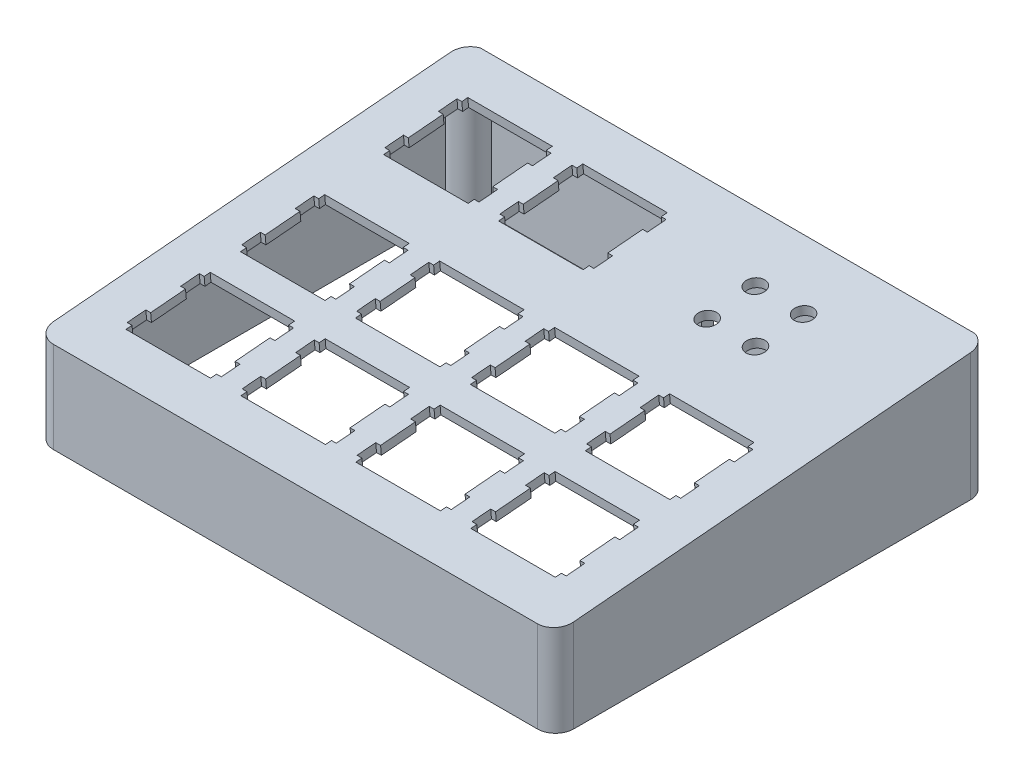
SolidWorks part; units mm, degrees
material "ABS"
ref_plane "Front" through (0, 0, 0) normal (0, 0, 1) x (1, 0, 0)
ref_plane "Top" through (0, 0, 0) normal (0, 1, 0) x (1, 0, 0)
ref_plane "Right" through (0, 0, 0) normal (1, 0, 0) x (0, 0, -1)
ref_axis "Axis1" through (80.9, 0, 0) along (-1, 0, 0)
ref_plane "Plane1" through (0, 0, 0) normal (0, 0.9962, 0.0872) x (1, 0, 0)
sketch "Sketch2" plane through (0, 0, 0) normal (0, 0.9962, 0.0872) x (1, 0, 0)
  line L1 (-43.1005, -35.9565) -> (43.1005, -35.9565)
  line L2 (-43.1005, -35.9565) -> (-43.1005, 35.9565)
  line L3 (-43.1005, 35.9565) -> (43.1005, 35.9565)
  line L4 (43.1005, -35.9565) -> (43.1005, 35.9565)
  line L5 (-43.1005, -35.9565) -> (43.1005, 35.9565) construction
  line L6 (-43.1005, 35.9565) -> (43.1005, -35.9565) construction
  point P0 (0, 0)
  dimension "D1" = 71.913
  dimension "D2" = 86.201
extrude "Boss-Extrude1" add sketch "Sketch2" along normal mid plane 1.5
sketch "Sketch7" plane through (0, 0.7471, 0.0654) normal (0, 0.9962, 0.0872) x (1, 0, 0)
  line L0 (16.5245, -2.3805) -> (21.5745, -2.3805) construction
  line L1 (19.0495, -2.3805) -> (19.0495, 21.432) construction
  line L2 (15.0495, 25.432) -> (23.0495, 25.432) construction
  line L3 (15.0495, 25.432) -> (15.0495, 17.432) construction
  line L4 (15.0495, 17.432) -> (23.0495, 17.432) construction
  line L5 (23.0495, 25.432) -> (23.0495, 17.432) construction
  line L6 (15.0495, 25.432) -> (23.0495, 17.432) construction
  line L7 (15.0495, 17.432) -> (23.0495, 25.432) construction
  line L8 (-43.1005, 35.9565) -> (-43.1005, -35.9565) construction
  line L9 (-43.1005, -35.9565) -> (43.1005, -35.9565) construction
  circle A0 centre (15.0495, 25.432) radius 1.5635
  circle A1 centre (23.0495, 25.432) radius 1.5635
  circle A2 centre (23.0495, 17.432) radius 1.5635
  circle A3 centre (15.0495, 17.432) radius 1.5635
  point P5 (-2.5255, 21.432)
  line B0 (43.1005, -35.9565) -> (-43.1005, -35.9565)
  line B1 (-43.1005, -35.9565) -> (-43.1005, 35.9565)
  line B2 (-43.1005, 35.9565) -> (43.1005, 35.9565)
  line B3 (43.1005, 35.9565) -> (43.1005, -35.9565)
  line B4 (21.5745, -14.4305) -> (21.5745, -15.4305)
  line B5 (21.5745, -15.4305) -> (20.7745, -15.4305)
  line B6 (20.7745, -15.4305) -> (20.7745, -18.5305)
  line B7 (20.7745, -18.5305) -> (21.5745, -18.5305)
  line B8 (21.5745, -18.5305) -> (21.5745, -24.3305)
  line B9 (21.5745, -24.3305) -> (20.7745, -24.3305)
  line B10 (20.7745, -24.3305) -> (20.7745, -27.4305)
  line B11 (20.7745, -27.4305) -> (21.5745, -27.4305)
  line B12 (21.5745, -27.4305) -> (21.5745, -28.4305)
  line B13 (21.5745, -28.4305) -> (35.5745, -28.4305)
  line B14 (35.5745, -28.4305) -> (35.5745, -27.4305)
  line B15 (35.5745, -27.4305) -> (36.3745, -27.4305)
  line B16 (36.3745, -27.4305) -> (36.3745, -24.3305)
  line B17 (36.3745, -24.3305) -> (35.5745, -24.3305)
  line B18 (35.5745, -24.3305) -> (35.5745, -18.5305)
  line B19 (35.5745, -18.5305) -> (36.3745, -18.5305)
  line B20 (36.3745, -18.5305) -> (36.3745, -15.4305)
  line B21 (36.3745, -15.4305) -> (35.5745, -15.4305)
  line B22 (35.5745, -15.4305) -> (35.5745, -14.4305)
  line B23 (35.5745, -14.4305) -> (21.5745, -14.4305)
  line B24 (2.5245, -14.4305) -> (2.5245, -15.4305)
  line B25 (2.5245, -15.4305) -> (1.7245, -15.4305)
  line B26 (1.7245, -15.4305) -> (1.7245, -18.5305)
  line B27 (1.7245, -18.5305) -> (2.5245, -18.5305)
  line B28 (2.5245, -18.5305) -> (2.5245, -24.3305)
  line B29 (2.5245, -24.3305) -> (1.7245, -24.3305)
  line B30 (1.7245, -24.3305) -> (1.7245, -27.4305)
  line B31 (1.7245, -27.4305) -> (2.5245, -27.4305)
  line B32 (2.5245, -27.4305) -> (2.5245, -28.4305)
  line B33 (2.5245, -28.4305) -> (16.5245, -28.4305)
  line B34 (16.5245, -28.4305) -> (16.5245, -27.4305)
  line B35 (16.5245, -27.4305) -> (17.3245, -27.4305)
  line B36 (17.3245, -27.4305) -> (17.3245, -24.3305)
  line B37 (17.3245, -24.3305) -> (16.5245, -24.3305)
  line B38 (16.5245, -24.3305) -> (16.5245, -18.5305)
  line B39 (16.5245, -18.5305) -> (17.3245, -18.5305)
  line B40 (17.3245, -18.5305) -> (17.3245, -15.4305)
  line B41 (17.3245, -15.4305) -> (16.5245, -15.4305)
  line B42 (16.5245, -15.4305) -> (16.5245, -14.4305)
  line B43 (16.5245, -14.4305) -> (2.5245, -14.4305)
  line B44 (-16.5255, -14.4305) -> (-16.5255, -15.4305)
  line B45 (-16.5255, -15.4305) -> (-17.3255, -15.4305)
  line B46 (-17.3255, -15.4305) -> (-17.3255, -18.5305)
  line B47 (-17.3255, -18.5305) -> (-16.5255, -18.5305)
  line B48 (-16.5255, -18.5305) -> (-16.5255, -24.3305)
  line B49 (-16.5255, -24.3305) -> (-17.3255, -24.3305)
  line B50 (-17.3255, -24.3305) -> (-17.3255, -27.4305)
  line B51 (-17.3255, -27.4305) -> (-16.5255, -27.4305)
  line B52 (-16.5255, -27.4305) -> (-16.5255, -28.4305)
  line B53 (-16.5255, -28.4305) -> (-2.5255, -28.4305)
  line B54 (-2.5255, -28.4305) -> (-2.5255, -27.4305)
  line B55 (-2.5255, -27.4305) -> (-1.7255, -27.4305)
  line B56 (-1.7255, -27.4305) -> (-1.7255, -24.3305)
  line B57 (-1.7255, -24.3305) -> (-2.5255, -24.3305)
  line B58 (-2.5255, -24.3305) -> (-2.5255, -18.5305)
  line B59 (-2.5255, -18.5305) -> (-1.7255, -18.5305)
  line B60 (-1.7255, -18.5305) -> (-1.7255, -15.4305)
  line B61 (-1.7255, -15.4305) -> (-2.5255, -15.4305)
  line B62 (-2.5255, -15.4305) -> (-2.5255, -14.4305)
  line B63 (-2.5255, -14.4305) -> (-16.5255, -14.4305)
  line B64 (-35.5765, -14.4305) -> (-35.5765, -15.4305)
  line B65 (-35.5765, -15.4305) -> (-36.3765, -15.4305)
  line B66 (-36.3765, -15.4305) -> (-36.3765, -18.5305)
  line B67 (-36.3765, -18.5305) -> (-35.5765, -18.5305)
  line B68 (-35.5765, -18.5305) -> (-35.5765, -24.3305)
  line B69 (-35.5765, -24.3305) -> (-36.3765, -24.3305)
  line B70 (-36.3765, -24.3305) -> (-36.3765, -27.4305)
  line B71 (-36.3765, -27.4305) -> (-35.5765, -27.4305)
  line B72 (-35.5765, -27.4305) -> (-35.5765, -28.4305)
  line B73 (-35.5765, -28.4305) -> (-21.5755, -28.4305)
  line B74 (-21.5755, -28.4305) -> (-21.5755, -27.4305)
  line B75 (-21.5755, -27.4305) -> (-20.7755, -27.4305)
  line B76 (-20.7755, -27.4305) -> (-20.7755, -24.3305)
  line B77 (-20.7755, -24.3305) -> (-21.5755, -24.3305)
  line B78 (-21.5755, -24.3305) -> (-21.5755, -18.5305)
  line B79 (-21.5755, -18.5305) -> (-20.7755, -18.5305)
  line B80 (-20.7755, -18.5305) -> (-20.7755, -15.4305)
  line B81 (-20.7755, -15.4305) -> (-21.5755, -15.4305)
  line B82 (-21.5755, -15.4305) -> (-21.5755, -14.4305)
  line B83 (-21.5755, -14.4305) -> (-35.5765, -14.4305)
  line B84 (21.5745, 4.6195) -> (21.5745, 3.6195)
  line B85 (21.5745, 3.6195) -> (20.7745, 3.6195)
  line B86 (20.7745, 3.6195) -> (20.7745, 0.5195)
  line B87 (20.7745, 0.5195) -> (21.5745, 0.5195)
  line B88 (21.5745, 0.5195) -> (21.5745, -5.2805)
  line B89 (21.5745, -5.2805) -> (20.7745, -5.2805)
  line B90 (20.7745, -5.2805) -> (20.7745, -8.3805)
  line B91 (20.7745, -8.3805) -> (21.5745, -8.3805)
  line B92 (21.5745, -8.3805) -> (21.5745, -9.3805)
  line B93 (21.5745, -9.3805) -> (35.5745, -9.3805)
  line B94 (35.5745, -9.3805) -> (35.5745, -8.3805)
  line B95 (35.5745, -8.3805) -> (36.3745, -8.3805)
  line B96 (36.3745, -8.3805) -> (36.3745, -5.2805)
  line B97 (36.3745, -5.2805) -> (35.5745, -5.2805)
  line B98 (35.5745, -5.2805) -> (35.5745, 0.5195)
  line B99 (35.5745, 0.5195) -> (36.3745, 0.5195)
  line B100 (36.3745, 0.5195) -> (36.3745, 3.6195)
  line B101 (36.3745, 3.6195) -> (35.5745, 3.6195)
  line B102 (35.5745, 3.6195) -> (35.5745, 4.6195)
  line B103 (35.5745, 4.6195) -> (21.5745, 4.6195)
  line B104 (2.5245, 4.6195) -> (2.5245, 3.6195)
  line B105 (2.5245, 3.6195) -> (1.7245, 3.6195)
  line B106 (1.7245, 3.6195) -> (1.7245, 0.5195)
  line B107 (1.7245, 0.5195) -> (2.5245, 0.5195)
  line B108 (2.5245, 0.5195) -> (2.5245, -5.2805)
  line B109 (2.5245, -5.2805) -> (1.7245, -5.2805)
  line B110 (1.7245, -5.2805) -> (1.7245, -8.3805)
  line B111 (1.7245, -8.3805) -> (2.5245, -8.3805)
  line B112 (2.5245, -8.3805) -> (2.5245, -9.3805)
  line B113 (2.5245, -9.3805) -> (16.5245, -9.3805)
  line B114 (16.5245, -9.3805) -> (16.5245, -8.3805)
  line B115 (16.5245, -8.3805) -> (17.3245, -8.3805)
  line B116 (17.3245, -8.3805) -> (17.3245, -5.2805)
  line B117 (17.3245, -5.2805) -> (16.5245, -5.2805)
  line B118 (16.5245, -5.2805) -> (16.5245, 0.5195)
  line B119 (16.5245, 0.5195) -> (17.3245, 0.5195)
  line B120 (17.3245, 0.5195) -> (17.3245, 3.6195)
  line B121 (17.3245, 3.6195) -> (16.5245, 3.6195)
  line B122 (16.5245, 3.6195) -> (16.5245, 4.6195)
  line B123 (16.5245, 4.6195) -> (2.5245, 4.6195)
  line B124 (-16.5255, 4.6195) -> (-16.5255, 3.6195)
  line B125 (-16.5255, 3.6195) -> (-17.3255, 3.6195)
  line B126 (-17.3255, 3.6195) -> (-17.3255, 0.5195)
  line B127 (-17.3255, 0.5195) -> (-16.5255, 0.5195)
  line B128 (-16.5255, 0.5195) -> (-16.5255, -5.2805)
  line B129 (-16.5255, -5.2805) -> (-17.3255, -5.2805)
  line B130 (-17.3255, -5.2805) -> (-17.3255, -8.3805)
  line B131 (-17.3255, -8.3805) -> (-16.5255, -8.3805)
  line B132 (-16.5255, -8.3805) -> (-16.5255, -9.3805)
  line B133 (-16.5255, -9.3805) -> (-2.5255, -9.3805)
  line B134 (-2.5255, -9.3805) -> (-2.5255, -8.3805)
  line B135 (-2.5255, -8.3805) -> (-1.7255, -8.3805)
  line B136 (-1.7255, -8.3805) -> (-1.7255, -5.2805)
  line B137 (-1.7255, -5.2805) -> (-2.5255, -5.2805)
  line B138 (-2.5255, -5.2805) -> (-2.5255, 0.5195)
  line B139 (-2.5255, 0.5195) -> (-1.7255, 0.5195)
  line B140 (-1.7255, 0.5195) -> (-1.7255, 3.6195)
  line B141 (-1.7255, 3.6195) -> (-2.5255, 3.6195)
  line B142 (-2.5255, 3.6195) -> (-2.5255, 4.6195)
  line B143 (-2.5255, 4.6195) -> (-16.5255, 4.6195)
  line B144 (-35.5765, 4.6195) -> (-35.5765, 3.6195)
  line B145 (-35.5765, 3.6195) -> (-36.3765, 3.6195)
  line B146 (-36.3765, 3.6195) -> (-36.3765, 0.5195)
  line B147 (-36.3765, 0.5195) -> (-35.5765, 0.5195)
  line B148 (-35.5765, 0.5195) -> (-35.5765, -5.2805)
  line B149 (-35.5765, -5.2805) -> (-36.3765, -5.2805)
  line B150 (-36.3765, -5.2805) -> (-36.3765, -8.3805)
  line B151 (-36.3765, -8.3805) -> (-35.5765, -8.3805)
  line B152 (-35.5765, -8.3805) -> (-35.5765, -9.3805)
  line B153 (-35.5765, -9.3805) -> (-21.5755, -9.3805)
  line B154 (-21.5755, -9.3805) -> (-21.5755, -8.3805)
  line B155 (-21.5755, -8.3805) -> (-20.7755, -8.3805)
  line B156 (-20.7755, -8.3805) -> (-20.7755, -5.2805)
  line B157 (-20.7755, -5.2805) -> (-21.5755, -5.2805)
  line B158 (-21.5755, -5.2805) -> (-21.5755, 0.5195)
  line B159 (-21.5755, 0.5195) -> (-20.7755, 0.5195)
  line B160 (-20.7755, 0.5195) -> (-20.7755, 3.6195)
  line B161 (-20.7755, 3.6195) -> (-21.5755, 3.6195)
  line B162 (-21.5755, 3.6195) -> (-21.5755, 4.6195)
  line B163 (-21.5755, 4.6195) -> (-35.5765, 4.6195)
  line B164 (-16.5255, 28.4325) -> (-16.5255, 27.4325)
  line B165 (-16.5255, 27.4325) -> (-17.3255, 27.4325)
  line B166 (-17.3255, 27.4325) -> (-17.3255, 24.3315)
  line B167 (-17.3255, 24.3315) -> (-16.5255, 24.3315)
  line B168 (-16.5255, 24.3315) -> (-16.5255, 18.5325)
  line B169 (-16.5255, 18.5325) -> (-17.3255, 18.5325)
  line B170 (-17.3255, 18.5325) -> (-17.3255, 15.4315)
  line B171 (-17.3255, 15.4315) -> (-16.5255, 15.4315)
  line B172 (-16.5255, 15.4315) -> (-16.5255, 14.4315)
  line B173 (-16.5255, 14.4315) -> (-2.5255, 14.4315)
  line B174 (-2.5255, 14.4315) -> (-2.5255, 15.4315)
  line B175 (-2.5255, 15.4315) -> (-1.7255, 15.4315)
  line B176 (-1.7255, 15.4315) -> (-1.7255, 18.5325)
  line B177 (-1.7255, 18.5325) -> (-2.5255, 18.5325)
  line B178 (-2.5255, 18.5325) -> (-2.5255, 24.3315)
  line B179 (-2.5255, 24.3315) -> (-1.7255, 24.3315)
  line B180 (-1.7255, 24.3315) -> (-1.7255, 27.4325)
  line B181 (-1.7255, 27.4325) -> (-2.5255, 27.4325)
  line B182 (-2.5255, 27.4325) -> (-2.5255, 28.4325)
  line B183 (-2.5255, 28.4325) -> (-16.5255, 28.4325)
  line B184 (-35.5765, 28.4325) -> (-35.5765, 27.4325)
  line B185 (-35.5765, 27.4325) -> (-36.3765, 27.4325)
  line B186 (-36.3765, 27.4325) -> (-36.3765, 24.3315)
  line B187 (-36.3765, 24.3315) -> (-35.5765, 24.3315)
  line B188 (-35.5765, 24.3315) -> (-35.5765, 18.5325)
  line B189 (-35.5765, 18.5325) -> (-36.3765, 18.5325)
  line B190 (-36.3765, 18.5325) -> (-36.3765, 15.4315)
  line B191 (-36.3765, 15.4315) -> (-35.5765, 15.4315)
  line B192 (-35.5765, 15.4315) -> (-35.5765, 14.4315)
  line B193 (-35.5765, 14.4315) -> (-21.5755, 14.4315)
  line B194 (-21.5755, 14.4315) -> (-21.5755, 15.4315)
  line B195 (-21.5755, 15.4315) -> (-20.7755, 15.4315)
  line B196 (-20.7755, 15.4315) -> (-20.7755, 18.5325)
  line B197 (-20.7755, 18.5325) -> (-21.5755, 18.5325)
  line B198 (-21.5755, 18.5325) -> (-21.5755, 24.3315)
  line B199 (-21.5755, 24.3315) -> (-20.7755, 24.3315)
  line B200 (-20.7755, 24.3315) -> (-20.7755, 27.4325)
  line B201 (-20.7755, 27.4325) -> (-21.5755, 27.4325)
  line B202 (-21.5755, 27.4325) -> (-21.5755, 28.4325)
  line B203 (-21.5755, 28.4325) -> (-35.5765, 28.4325)
  dimension "D1" = 3.127
  dimension "D2" = 8
sketch_block_instance "Block1-1"
sketch_block "Block1"
extrude "Cut-Extrude1" cut sketch "Sketch7" against normal up to next contours B42 B43 B24 B25 B26 B27 B28 B29 B30 B31 B32 B33 B34 B35 B36 B37 B38 B39 B40 B41 | B22 B23 B4 B5 B6 B7 B8 B9 B10 B11 B12 B13 B14 B15 B16 B17 B18 B19 B20 B21 | B122 B123 B104 B105 B106 B107 B108 B109 B110 B111 B112 B113 B114 B115 B116 B117 B118 B119 B120 B121 | B62 B63 B44 B45 B46 B47 B48 B49 B50 B51 B52 B53 B54 B55 B56 B57 B58 B59 B60 B61 | B142 B143 B124 B125 B126 B127 B128 B129 B130 B131 B132 B133 B134 B135 B136 B137 B138 B139 B140 B141 | B82 B83 B64 B65 B66 B67 B68 B69 B70 B71 B72 B73 B74 B75 B76 B77 B78 B79 B80 B81 | B162 B163 B144 B145 B146 B147 B148 B149 B150 B151 B152 B153 B154 B155 B156 B157 B158 B159 B160 B161 | B102 B103 B84 B85 B86 B87 B88 B89 B90 B91 B92 B93 B94 B95 B96 B97 B98 B99 B100 B101 | B202 B203 B184 B185 B186 B187 B188 B189 B190 B191 B192 B193 B194 B195 B196 B197 B198 B199 B200 B201 | B182 B183 B164 B165 B166 B167 B168 B169 B170 B171 B172 B173 B174 B175 B176 B177 B178 B179 B180 B181 | A3 | A0 | A1 | A2 region at (15.0495, 2.9637, -25.2699) region at (23.0495, 2.9637, -25.2699) region at (23.0495, 2.2664, -17.3003) region at (15.0495, 2.2664, -17.3003) region at (28.5745, -1.1206, 21.4143) region at (9.5245, -1.1206, 21.4143) region at (-9.5255, -1.1206, 21.4143) region at (-28.576, -1.1206, 21.4143) region at (28.5745, 0.5397, 2.4368) region at (9.5245, 0.5397, 2.4368) region at (-9.5255, 0.5397, 2.4368) region at (-28.576, 0.5397, 2.4368) region at (-9.5255, 2.6151, -21.2851) region at (-28.576, 2.6151, -21.2851)
ref_plane "Plane2" through (0, -17.5, 0) normal (0, -1, 0) x (-1, 0, 0)
sketch "Sketch3" plane through (0, -17.5, 0) normal (0, -1, 0) x (-1, 0, 0)
  line L5 (-43.1005, 35.885) -> (43.1005, 35.885)
  line L6 (-43.1005, 35.885) -> (-43.1005, -35.885)
  line L7 (-43.1005, -35.885) -> (43.1005, -35.885)
  line L8 (43.1005, 35.885) -> (43.1005, -35.885)
extrude "Extrude-Thin1" add sketch "Sketch3" against normal up to next thin thin type one direction reverse wall 2
fillet "Fillet1" radius 3 4 edges at (43.1005, -7.5567, -35.885) (-43.1005, -7.5567, -35.885) (43.1005, -9.9433, 35.885) (-43.1005, -9.9433, 35.885)
sketch "Sketch4" plane through (0, -17.5, 0) normal (0, -1, 0) x (1, 0, 0)
  circle A1 centre (-40.1005, 32.885) radius 3
  arc A2 (-40.1005, 35.885) -> (-43.1005, 32.885) centre (-40.1005, 32.885) ccw construction
  circle A3 centre (40.1005, 32.885) radius 3
  circle A4 centre (40.1005, -32.885) radius 3
  circle A5 centre (-40.1005, -32.885) radius 3
  arc A6 (43.1005, 32.885) -> (40.1005, 35.885) centre (40.1005, 32.885) ccw construction
extrude "Boss-Extrude2" add sketch "Sketch4" against normal up to next
hole_wizard "Tap Drill for #2-56 Tap1" positions "Sketch5" profile "Sketch6" hole size "#2-56" standard "ANSI Inch"
sketch "Sketch5" plane through (0, -17.5, 0) normal (0, -1, 0) x (-1, 0, 0)
  point P0 (40.1005, -32.885)
  point P3 (-40.1005, -32.885)
  point P6 (-40.1005, 32.885)
  point P9 (40.1005, 32.885)
sketch "Sketch6" plane through (-40.1005, -17.5, 32.885) normal (1, 0, 0) x (0, 0, -1)
  line L0 (0, 0) -> (0, 13.2342)
  line L1 (0, 13.2342) -> (0.889, 12.7)
  line L2 (0.889, 12.7) -> (0.889, 0)
  line L5 (0.889, 0) -> (0, 0)
  line L10 (0, 13.2342) -> (-0.889, 12.7) construction
  line L11 (0, -6.35) -> (0, 107.95) construction
  dimension "Hole Dia." = 1.778
  dimension "Hole Depth" = 12.7
  dimension "Drill Angle" = 118
sketch "Sketch8" plane through (0, 0, -35.885) normal (0, 0, -1) x (-1, 0, 0)
  line L0 (0, -17.5) -> (0, -15) construction
  line L1 (40.1005, -17.5) -> (-40.1005, -17.5) construction
  line L2 (-2.5, -15) -> (-2.5, -17.5)
  line L3 (2.5, -15) -> (2.5, -17.5)
  line L4 (2.5, -17.5) -> (-2.5, -17.5)
  arc A0 (2.5, -15) -> (-2.5, -15) centre (0, -15) ccw
  dimension "D1" = 5
extrude "Cut-Extrude2" cut sketch "Sketch8" against normal up to next
